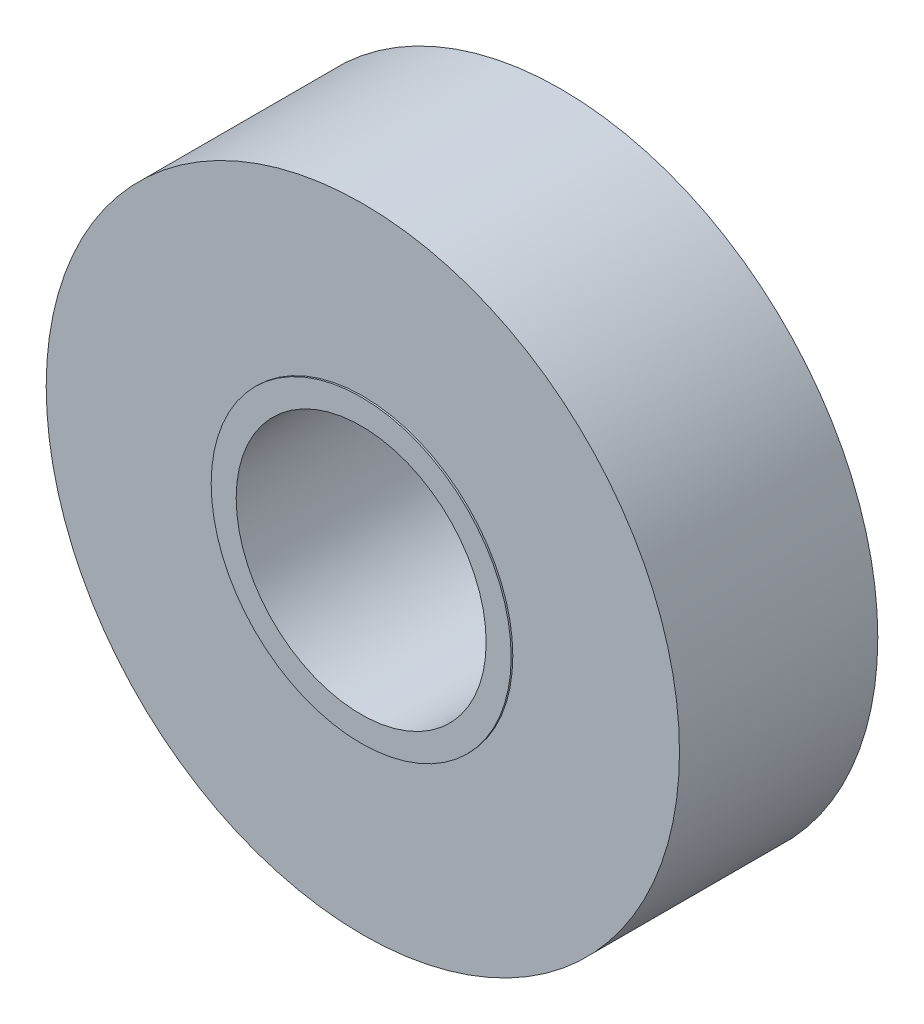
SolidWorks part; units mm, degrees
ref_plane "Alzado" through (0, 0, 0) normal (0, 0, 1) x (1, 0, 0)
ref_plane "Planta" through (0, 0, 0) normal (0, 1, 0) x (1, 0, 0)
ref_plane "Vista lateral" through (0, 0, 0) normal (1, 0, 0) x (0, 0, -1)
sketch "Croquis1" plane through (0, 0, 0) normal (0, 0, 1) x (1, 0, 0)
  circle A0 centre (0, 0) radius 7.5
  circle A1 centre (0, 0) radius 9
  circle A3 centre (0, 0) radius 9
  circle A4 centre (0, 0) radius 1.5
  circle A5 centre (0, 0) radius 7.4545
  circle A6 centre (0, 0) radius 7.5
  dimension "D1" = 15
  dimension "D2" = 18
  dimension "D3" = 3
extrude "Saliente-Extruir1" add sketch "Croquis1" along normal blind 12 contours A1 A0 region at (-8.7454, 0, 0)
sketch "Croquis2" plane through (0, 0, 0) normal (0, 0, 1) x (1, 0, 0)
  circle A0 centre (0, 0) radius 7.5
extrude "Saliente-Extruir2" add sketch "Croquis2" along normal blind 1 and the other way blind 0.1
sketch "Croquis3" plane through (0, 0, 0) normal (0, 0, 1) x (1, 0, 0)
  circle A0 centre (0, 0) radius 5.2
  circle A1 centre (0, 0) radius 1.5
  dimension "D1" = 10.4
  dimension "D2" = 3
extrude "Saliente-Extruir4" add sketch "Croquis3" against normal blind 3 contours A0 | A1
sketch "Croquis4" plane through (0, 0, 0) normal (0, 0, -1) x (-1, 0, 0)
  circle A0 centre (0, 0) radius 9
  circle A1 centre (0, 0) radius 19
  dimension "D1" = 38
extrude "Saliente-Extruir5" add sketch "Croquis4" against normal blind 11.9
sketch "Croquis6" plane through (0, 0, -3) normal (0, 0, -1) x (-1, 0, 0)
  circle A0 centre (0, 0) radius 1.5
extrude "Cortar-Extruir1" [suppressed] cut sketch "Croquis6" against normal blind 10
